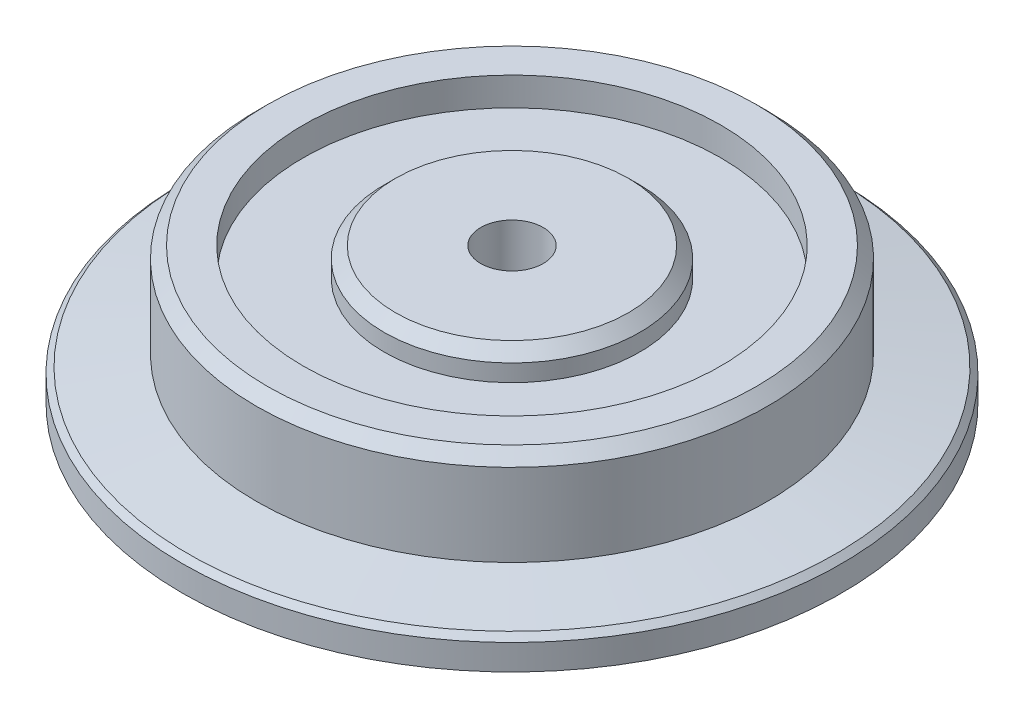
SolidWorks part; units mm, degrees
other "标注1"
sketch "草图3" plane through (-22.25, 4, -10) normal (-0.231, 0.6469, -0.7268) x (-0.9696, -0.2151, 0.1167)
ref_plane "前视基准面" through (0, 0, 0) normal (0, 0, 1) x (1, 0, 0)
ref_plane "上视基准面" through (0, 0, 0) normal (0, 1, 0) x (1, 0, 0)
ref_plane "右视基准面" through (0, 0, 0) normal (1, 0, 0) x (0, 0, -1)
other "Configuration Table"
sketch "草图4" plane through (0, 0, 0) normal (0, 1, 0) x (1, 0, 0)
  circle A0 centre (0, 0) radius 11.6
  circle A1 centre (0, 0) radius 1.1
  circle A2 centre (0, 0) radius 9
  dimension "D1" = 23.2
  dimension "D2" = 2.2
  dimension "D3" = 18
extrude "凸台-拉伸1" add sketch "草图4" along normal blind 1.1 contours A0 | A1
extrude "凸台-拉伸2" add sketch "草图4<3>" along normal blind 3.3 from offset 1.5 contours A2 | A1
sketch "草图4<3>" plane through (0, 0, 0) normal (0, 1, 0) x (1, 0, 0) same geometry as "草图4"
chamfer "倒角1" distance 0.2 angle 45 1 edges at (0, 1.1, 11.6)
loft "放样1" add section edge at (0, 1.5, 9) section edge at (0, 1.1, 11.4)
sketch "草图6" plane through (0, 4.8, 0) normal (0, 1, 0) x (1, 0, 0)
  circle A0 centre (0, 0) radius 7.35
  circle A1 centre (0, 0) radius 4.5
  dimension "D1" = 14.7
  dimension "D2" = 9
extrude "切除-拉伸1" cut sketch "草图6" against normal blind 1 contours A0 A1 region at (-7.1421, 4.8, 0)
chamfer "倒角2" distance 0.4 angle 45 2 edges at (0, 4.8, 4.5) (0, 4.8, 9)
extrude "切除-拉伸2" cut sketch "草图4<4>" along normal through all contours A1
sketch "草图4<4>" plane through (0, 0, 0) normal (0, 1, 0) x (1, 0, 0) same geometry as "草图4"
chamfer "倒角3" distance 0.5 angle 45 1 edges at (0, 0, 1.1)
